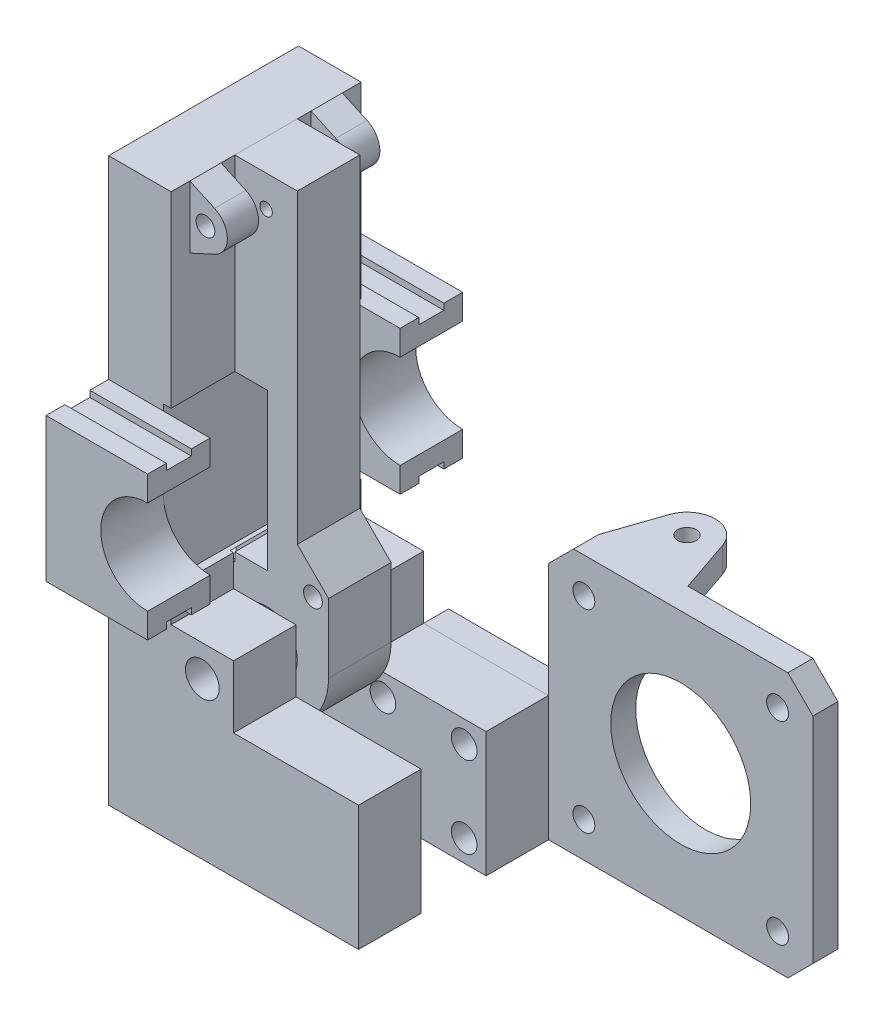
SolidWorks part; units mm, degrees
ref_plane "Front Plane" through (0, 0, 0) normal (0, 0, 1) x (1, 0, 0)
ref_plane "Top Plane" through (0, 0, 0) normal (0, 1, 0) x (1, 0, 0)
ref_plane "Right Plane" through (0, 0, 0) normal (1, 0, 0) x (0, 0, -1)
sketch "Sketch1" plane through (0, 0, 0) normal (0, 0, 1) x (1, 0, 0)
  line L0 (-10, 0) -> (-10, -10)
  line L2 (0, 0) -> (0, 40)
  line L3 (0, 40) -> (-10, 40)
  line L4 (-10, 0) -> (-10, 40)
  line L6 (10, -10) -> (10, 0)
  line L7 (10, 0) -> (0, 0)
  line L8 (0, 0) -> (10, -10) construction
  line L9 (10, -10) -> (30, -10)
  line L11 (-10, -10) -> (-10, -30)
  line L12 (-10, -30) -> (30, -30)
  line L13 (30, -10) -> (30, -30)
  line L14 (-10, -10) -> (30, -30) construction
  line L15 (-10, -30) -> (30, -10) construction
  circle A0 centre (5, -5) radius 2.7
  point P13 (10, -20)
  dimension "D5" = 5.4
  dimension "D1" = 10
  dimension "D2" = 40
  dimension "D3" = 10
  dimension "D4" = 10
  dimension "D6" = 20
  dimension "D7" = 40
extrude "Boss-Extrude1" add sketch "Sketch1" against normal blind 10 from offset 5.2 offset against normal yes
extrude "Boss-Extrude3" add sketch "Sketch1<2>" along normal blind 10 from offset 5.2 separate body
sketch "Sketch1<2>" plane through (0, 0, 0) normal (0, 0, 1) x (1, 0, 0) same geometry as "Sketch1"
sketch "Sketch2" plane through (0, 0, 0) normal (0, 0, 1) x (1, 0, 0)
  line L0 (0, 0) -> (0, 40) construction
  line L1 (0, 60) -> (10, 60)
  line L2 (0, 60) -> (0, 3.6603)
  line L4 (10, 60) -> (10, 3.6603)
  line L5 (0, 60) -> (10, 3.6603) construction
  line L6 (0, 3.6603) -> (10, 60) construction
  line L7 (0, 40) -> (-10, 40) construction
  circle A0 centre (5, -5) radius 5
  arc A1 (0, 3.6603) -> (10, 3.6603) centre (5, -5) ccw
  circle A2 centre (5, 55) radius 1
  point P8 (5, 31.8301)
  point P12 (5, 60)
  dimension "D1" = 10
  dimension "D2" = 5
  dimension "D5" = 2
  dimension "D3" = 20
  dimension "D4" = 5
extrude "Boss-Extrude2" add sketch "Sketch2" along normal mid plane 10 separate body
sketch "Sketch3" plane through (0, 0, 0) normal (0, 0, 1) x (1, 0, 0)
  line L0 (0, 0) -> (0, 40) construction
  line L1 (-10, 40) -> (0, 40)
  line L2 (-10, 40) -> (-10, -4.4437)
  line L3 (-10, -4.4437) -> (0, 5.5563)
  line L4 (0, 40) -> (0, 5.5563)
  line L5 (-10, 40) -> (-10, -30) construction
  circle A0 centre (5, -5) radius 11 construction
  arc A1 (0, 3.6603) -> (10, 3.6603) centre (5, -5) ccw construction
  dimension "D2" = 1
  dimension "D1" = 135
extrude "Boss-Extrude4" add sketch "Sketch3" along normal mid plane 10.4
sketch "Sketch4" plane through (0, 0, 0) normal (0, 0, 1) x (1, 0, 0)
  line L5 (0, 60) -> (0, 3.6603) construction
  line L6 (-1.25, 5) -> (1.25, 5)
  line L7 (-1.25, 5) -> (-1.25, 30)
  line L8 (-1.25, 30) -> (1.25, 30)
  line L9 (1.25, 5) -> (1.25, 30)
  line L10 (-1.25, 5) -> (1.25, 30) construction
  line L11 (-1.25, 30) -> (1.25, 5) construction
  arc A0 (0, 3.6603) -> (10, 3.6603) centre (5, -5) ccw construction
  point P0 (0, 17.5)
  point P7 (5, 5)
  point P13 (5, -5)
  dimension "D1" = 2.5
  dimension "D2" = 25
extrude "Cut-Extrude1" cut sketch "Sketch4" against normal through all both and the other way through all
sketch "Sketch5" plane through (0, 0, 0) normal (0, 0, 1) x (1, 0, 0)
  line L1 (6.25, 29) -> (-10, 29)
  line L2 (-10, 40) -> (-10, -30) construction
  line L3 (-10, 29) -> (-10, 6)
  line L4 (-10, 6) -> (6.25, 6)
  line L5 (6.25, 29) -> (6.25, 25)
  line L6 (6.25, 10) -> (6.25, 6)
  line L7 (-1.25, 5) -> (-1.25, 30) construction
  arc A0 (6.25, 25) -> (6.25, 10) centre (6.25, 17.5) ccw
  point P12 (-1.25, 17.5)
  dimension "D1" = 15
  dimension "D2" = 4
extrude "Boss-Extrude5" add sketch "Sketch5" along normal blind 10 from surface starting at face at (4.7917, 5.8333, 15.2)
extrude "Boss-Extrude6" add sketch "Sketch5<2>" against normal blind 10 from surface starting at face at (4.7917, 5.8333, -15.2)
sketch "Sketch5<2>" plane through (0, 0, 0) normal (0, 0, 1) x (1, 0, 0) same geometry as "Sketch5"
chamfer "Chamfer1" distance 5 angle 45 2 edges at (1.25, 17.5, -5) (1.25, 17.5, 5)
sketch "Sketch6" plane through (0, 0, 0) normal (0, 0, 1) x (1, 0, 0)
  line L0 (10, 3.6603) -> (10, 60) construction
  line L1 (15, -5) -> (15, 6.0355)
  line L2 (15, 6.0355) -> (10, 11.0355)
  line L3 (10, 11.0355) -> (10, 3.6603)
  circle A0 centre (12.5, 5) radius 2.5 construction
  arc A1 (0, 3.6603) -> (10, 3.6603) centre (5, -5) ccw construction
  circle A2 centre (12.5, 5) radius 1.5
  arc A3 (10, 3.6603) -> (15, -5) centre (5, -5) cw
  dimension "D1" = 5
  dimension "D3" = 3
  dimension "D2" = 45
extrude "Boss-Extrude7" add sketch "Sketch6" along normal mid plane 10 contours L3 A3 L1 L2 A2 region at (13.8057, 0.084, 0)
sketch "Sketch7" plane through (0, 0, 0) normal (0, 0, 1) x (1, 0, 0)
  line L1 (-10, 40) -> (0, 40)
  line L2 (-10, 40) -> (-10, 60)
  line L3 (-10, 60) -> (0, 60)
  line L4 (0, 40) -> (0, 60)
  line L5 (-10, 40) -> (0, 60) construction
  line L6 (-10, 60) -> (0, 40) construction
  point P4 (-5, 50)
extrude "Boss-Extrude8" add sketch "Sketch7" along normal mid plane 30.4
sketch "Sketch8" plane through (0, 0, -15.2) normal (0, 0, -1) x (-1, 0, 0)
  line L0 (-3.961, 51.8195) -> (0, 50)
  line L1 (0, 30) -> (0, 60) construction
  line L2 (-3.961, 58.1805) -> (0, 60)
  line L3 (0, 60) -> (0, 50)
  circle A0 centre (-2.5, 55) radius 1.5
  arc A1 (-3.961, 58.1805) -> (-3.961, 51.8195) centre (-2.5, 55) ccw
  circle A2 centre (-5, 55) radius 1 construction
  point P14 (-5, 55)
  dimension "D1" = 3
  dimension "D2" = 2
  dimension "D3" = 5
extrude "Boss-Extrude9" add sketch "Sketch8" along normal blind 5 from offset 8 offset against normal yes
mirror "Mirror1" about plane through (0, 0, 0) normal (0, 0, 1) of "Boss-Extrude9"
sketch "Sketch9" plane through (6.25, 0, 0) normal (1, 0, 0) x (0, 0, -1)
  line L0 (25.2, 29) -> (15.2, 29) construction
  line L1 (18.2, 30) -> (22.2, 30)
  line L2 (18.2, 30) -> (18.2, 28)
  line L3 (18.2, 28) -> (22.2, 28)
  line L4 (22.2, 30) -> (22.2, 28)
  line L5 (18.2, 30) -> (22.2, 28) construction
  line L6 (18.2, 28) -> (22.2, 30) construction
  line L7 (25.2, 6) -> (15.2, 6) construction
  line L8 (18.2, 5) -> (22.2, 5)
  line L9 (18.2, 5) -> (18.2, 7)
  line L10 (18.2, 7) -> (22.2, 7)
  line L11 (22.2, 5) -> (22.2, 7)
  line L12 (18.2, 5) -> (22.2, 7) construction
  line L13 (18.2, 7) -> (22.2, 5) construction
  line L14 (-25.2, 6) -> (-15.2, 6) construction
  line L15 (-22.2, 5) -> (-18.2, 5)
  line L16 (-22.2, 5) -> (-22.2, 7)
  line L17 (-22.2, 7) -> (-18.2, 7)
  line L18 (-18.2, 5) -> (-18.2, 7)
  line L19 (-22.2, 5) -> (-18.2, 7) construction
  line L20 (-22.2, 7) -> (-18.2, 5) construction
  line L21 (-25.2, 29) -> (-15.2, 29) construction
  line L22 (-22.2, 30) -> (-18.2, 30)
  line L23 (-22.2, 30) -> (-22.2, 28)
  line L24 (-22.2, 28) -> (-18.2, 28)
  line L25 (-18.2, 30) -> (-18.2, 28)
  line L26 (-22.2, 30) -> (-18.2, 28) construction
  line L27 (-22.2, 28) -> (-18.2, 30) construction
  point P0 (20.2, 29)
  point P7 (20.2, 6)
  point P14 (-20.2, 6)
  point P21 (-20.2, 29)
  dimension "D1" = 4
  dimension "D2" = 2
extrude "Cut-Extrude2" cut sketch "Sketch9" against normal through all
sketch "Sketch10" plane through (-10, 0, 0) normal (-1, 0, 0) x (0, 0, 1)
  line L1 (-12.2, 57) -> (12.2, 57) construction
  line L2 (-12.2, 57) -> (-12.2, -27) construction
  line L3 (-12.2, -27) -> (12.2, -27) construction
  line L4 (12.2, 57) -> (12.2, -27) construction
  line L5 (-12.2, 57) -> (12.2, -27) construction
  line L6 (-12.2, -27) -> (12.2, 57) construction
  line L7 (0, 57) -> (0, 60) construction
  line L9 (15.2, 60) -> (-15.2, 60) construction
  line L10 (12.2, -13.2466) -> (15.2, -13.2466) construction
  line L12 (15.2, 6) -> (15.2, -30) construction
  line L13 (8.6316, -27) -> (8.6316, -30) construction
  line L14 (15.2, -30) -> (5.2, -30) construction
  circle A0 centre (12.2, -27) radius 1.5
  circle A1 centre (-12.2, -27) radius 1.5
  circle A2 centre (-12.2, 57) radius 1.5
  circle A3 centre (12.2, 57) radius 1.5
  point P4 (0, 15)
  dimension "D2" = 3
  dimension "D1" = 3
extrude "Cut-Extrude3" cut sketch "Sketch10" against normal blind 8 draft 8
sketch "Sketch11" plane through (0, 0, -15.2) normal (0, 0, -1) x (-1, 0, 0)
  line L0 (-30, -20) -> (-26.5, -20) construction
  line L1 (-26.5, -13.5) -> (-13.5, -13.5) construction
  line L2 (-26.5, -13.5) -> (-26.5, -26.5) construction
  line L3 (-26.5, -26.5) -> (-13.5, -26.5) construction
  line L4 (-13.5, -13.5) -> (-13.5, -26.5) construction
  line L5 (-26.5, -13.5) -> (-13.5, -26.5) construction
  line L6 (-26.5, -26.5) -> (-13.5, -13.5) construction
  line L7 (-30, -30) -> (-30, -10) construction
  line L8 (-20, -10) -> (-20, -13.5) construction
  line L9 (-30, -10) -> (-10, -10) construction
  circle A0 centre (-26.5, -13.5) radius 2.05
  circle A1 centre (-13.5, -13.5) radius 2.05
  circle A2 centre (-13.5, -26.5) radius 2.05
  circle A3 centre (-26.5, -26.5) radius 2.05
  circle A4 centre (-13.5, -13.5) radius 1.75
  circle A5 centre (-13.5, -26.5) radius 1.75
  circle A6 centre (-26.5, -26.5) radius 1.75
  circle A7 centre (-26.5, -13.5) radius 1.75
  point P4 (-20, -20)
  dimension "D2" = 4.1
  dimension "D3" = 3.5
  dimension "D1" = 13
extrude "Cut-Extrude4" cut sketch "Sketch11" against normal up to next (10 mm away) contours A0 A7 | A1 A4 | A2 A5 | A3 A6 | A6 | A5 | A4 | A7 region at (28.492, -13.5, -15.2) region at (15.492, -13.5, -15.2) region at (15.492, -26.5, -15.2) region at (28.492, -26.5, -15.2) region at (13.5, -13.5, -15.2) region at (13.5, -26.5, -15.2) region at (26.5, -26.5, -15.2) region at (26.5, -13.5, -15.2)
sketch "Sketch12" plane through (0, 0, -15.2) normal (0, 0, -1) x (-1, 0, 0)
  line L0 (-30, 12.3) -> (-30, -10)
  line L1 (-10, -10) -> (-30, -10)
  line L2 (-10, -10) -> (-10, -30)
  line L3 (-10, -30) -> (-30, -30)
  line L5 (-10, -10) -> (-30, -30) construction
  line L6 (-10, -30) -> (-30, -10) construction
  line L7 (-30, -30) -> (-72.3, -30)
  line L9 (-30, 12.3) -> (-72.3, 12.3)
  line L10 (-72.3, -30) -> (-72.3, 12.3)
  line L11 (-30, -30) -> (-72.3, 12.3) construction
  line L12 (-30, 12.3) -> (-72.3, -30) construction
  line L13 (-35.65, -24.35) -> (-66.65, -24.35) construction
  line L14 (-35.65, -24.35) -> (-35.65, 6.65) construction
  line L15 (-35.65, 6.65) -> (-66.65, 6.65) construction
  line L16 (-66.65, -24.35) -> (-66.65, 6.65) construction
  line L17 (-35.65, -24.35) -> (-66.65, 6.65) construction
  line L18 (-35.65, 6.65) -> (-66.65, -24.35) construction
  circle A0 centre (-66.65, 6.65) radius 1.75
  circle A1 centre (-35.65, 6.65) radius 1.75
  circle A2 centre (-66.65, -24.35) radius 1.75
  circle A3 centre (-35.65, -24.35) radius 1.75
  circle A4 centre (-51.15, -8.85) radius 11.2
  point P4 (-20, -20)
  point P10 (-51.15, -8.85)
  point P11 (-51.15, -8.85)
  dimension "D3" = 3.5
  dimension "D4" = 22.4
  dimension "D1" = 42.3
  dimension "D2" = 31
extrude "Boss-Extrude10" add sketch "Sketch12" along normal blind 4 separate body
chamfer "Chamfer2" distance 4 angle 45 3 edges at (72.3, -30, -17.2) (72.3, 12.3, -17.2) (30, 12.3, -17.2)
extrude "Cut-Extrude5" cut sketch "Sketch11<3>" along normal through all contours A7 | A4 | A5 | A6 region at (13.5, -13.5, -15.2) region at (13.5, -26.5, -15.2) region at (26.5, -26.5, -15.2) region at (26.5, -13.5, -15.2)
sketch "Sketch11<3>" plane through (0, 0, -15.2) normal (0, 0, -1) x (-1, 0, 0) same geometry as "Sketch11"
sketch "Sketch14" plane through (0, 12.3, 0) normal (0, 1, 0) x (1, 0, 0)
  line L0 (34, 19.2) -> (68.3, 19.2) construction
  line L1 (34, 19.2) -> (36.8921, 27.6562)
  line L2 (45.4079, 27.6562) -> (48.3, 19.2)
  line L3 (34, 19.2) -> (48.3, 19.2)
  circle A0 centre (41.15, 26.2) radius 1.5
  arc A2 (36.8921, 27.6562) -> (45.4079, 27.6562) centre (41.15, 26.2) cw
  point P4 (51.15, 19.2)
  dimension "D2" = 3
  dimension "D4" = 3
  dimension "D1" = 10
  dimension "D3" = 7
extrude "Boss-Extrude11" add sketch "Sketch14" against normal blind 4
sketch "Sketch15" plane through (0, 5, 0) normal (0, 1, 0) x (1, 0, 0)
  line L0 (6.25, -5) -> (1.25, 0)
  line L1 (1.25, 0) -> (6.25, 5)
  line L2 (6.25, 5) -> (5.25, 5)
  line L3 (0, 5) -> (6.25, 5) construction
  line L4 (5.25, 5) -> (0.25, 0)
  line L5 (0.25, 0) -> (5.25, -5)
  line L6 (0, -5) -> (6.25, -5) construction
  line L7 (5.25, -5) -> (6.25, -5)
  point P4 (0, 0)
  dimension "D1" = 1
extrude "Boss-Extrude12" add sketch "Sketch15" along normal up to next
